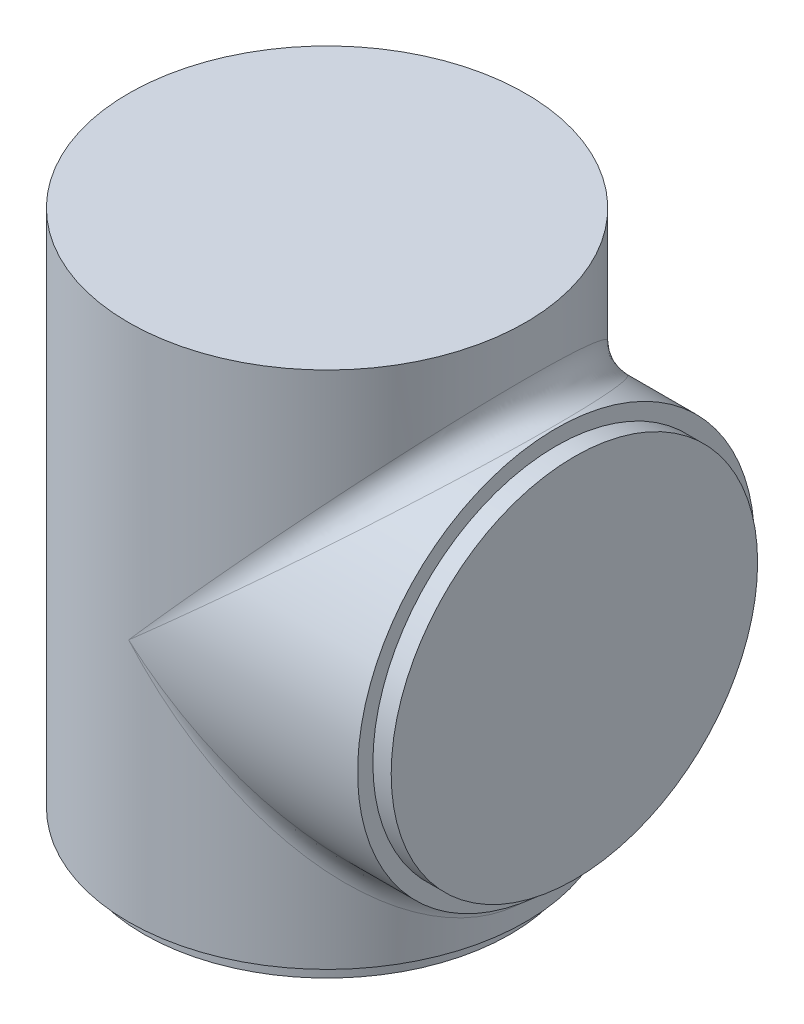
SolidWorks part; units mm, degrees
material "PP Copolymer"
ref_plane "Front Plane" through (0, 0, 0) normal (0, 0, 1) x (1, 0, 0)
ref_plane "Top Plane" through (0, 0, 0) normal (0, 1, 0) x (1, 0, 0)
ref_plane "Right Plane" through (0, 0, 0) normal (1, 0, 0) x (0, 0, -1)
sketch "Sketch1" plane through (0, 0, 0) normal (0, 1, 0) x (1, 0, 0)
  circle A0 centre (0, 0) radius 30
  dimension "D1" = 60
extrude "Boss-Extrude1" add sketch "Sketch1" along normal blind 3
sketch "Sketch2" plane through (0, 3, 0) normal (0, 1, 0) x (1, 0, 0)
  circle A0 centre (0, 0) radius 32.5
  dimension "D1" = 65
extrude "Boss-Extrude2" add sketch "Sketch2" along normal blind 85
sketch "Sketch3" plane through (0, 0, 0) normal (1, 0, 0) x (0, 0, -1)
  line L0 (-32.5, 43) -> (32.5, 43) construction
  line L1 (-32.5, 88) -> (-32.5, 3) construction
  line L2 (32.5, 3) -> (32.5, 88) construction
  line L3 (-30, 3) -> (30, 3) construction
  circle A0 centre (0, 43) radius 32.5
  dimension "D2" = 65
  dimension "D1" = 40
extrude "Boss-Extrude3" add sketch "Sketch3" along normal blind 37.5 contours A0
fillet "Fillet1" radius 4.5 2 edges at (32.5, 75.5, 0) (32.5, 10.5, 0)
sketch "Sketch5" plane through (37.5, 0, 0) normal (1, 0, 0) x (0, 0, -1)
  circle A0 centre (0, 43) radius 30
  dimension "D1" = 60
extrude "Boss-Extrude5" add sketch "Sketch5" along normal blind 3
